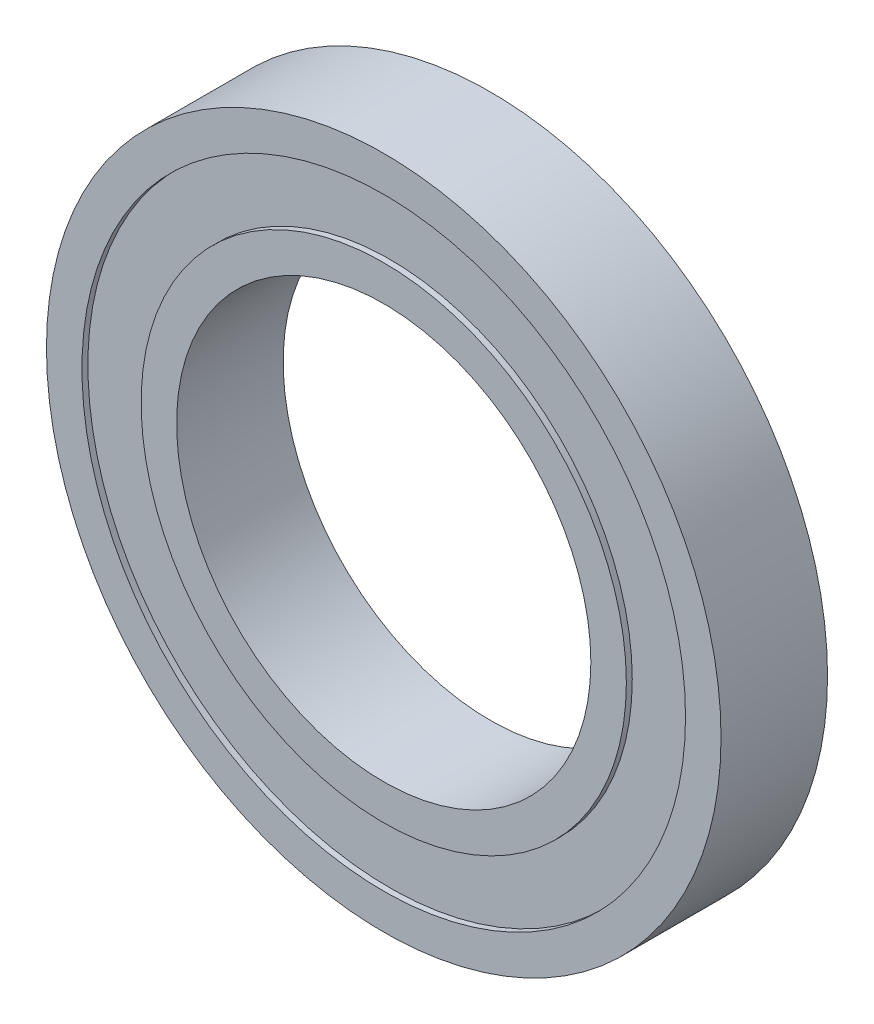
SolidWorks part; units mm, degrees
ref_plane "Front Plane" through (0, 0, 0) normal (1, 0, 0) x (0, 1, 0)
ref_plane "Top Plane" through (0, 0, 0) normal (0, 0, 1) x (0, 1, 0)
ref_plane "Right Plane" through (0, 0, 0) normal (0, 1, 0) x (-1, 0, 0)
sketch "Sketch1" plane through (0, 0, 0) normal (0, 0, 1) x (0, 1, 0)
  circle A0 centre (0, 0) radius 17.5
  circle A2 centre (0, 0) radius 28.5
  circle A3 centre (0, 0) radius 25.5
  circle A4 centre (0, 0) radius 20.5
  dimension "D1" = 57
  dimension "D2" = 35
  dimension "D3" = 3
  dimension "D4" = 3
extrude "Boss-Extrude1" add sketch "Sketch1" along normal blind 9 contours A4 A0 | A2 A3 region at (0, -27.6939, 0) region at (0, -19.9202, 0)
extrude "Boss-Extrude2" add sketch "Sketch1<3>" along normal blind 8 from offset 0.5 contours A3 A4 region at (0, -24.7788, 0)
sketch "Sketch1<3>" plane through (0, 0, 0) normal (0, 0, 1) x (0, 1, 0) same geometry as "Sketch1"
